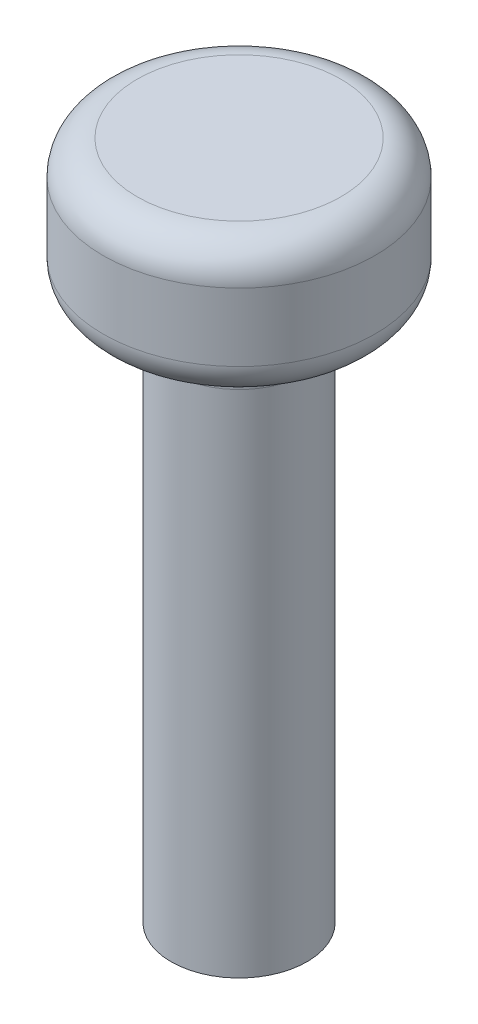
SolidWorks part; units mm, degrees
material "AISI 1020 Steel, Cold Rolled"
ref_plane "Front Plane" through (0, 0, 0) normal (0, 0, 1) x (1, 0, 0)
ref_plane "Top Plane" through (0, 0, 0) normal (0, 1, 0) x (1, 0, 0)
ref_plane "Right Plane" through (0, 0, 0) normal (1, 0, 0) x (0, 0, -1)
sketch "Sketch1" plane through (0, 0, 0) normal (0, 1, 0) x (1, 0, 0)
  circle A0 centre (0, 0) radius 1
  dimension "D1" = 2
extrude "Boss-Extrude1" add sketch "Sketch1" along normal blind 8
sketch "Sketch2" plane through (0, 8, 0) normal (0, 1, 0) x (1, 0, 0)
  circle A0 centre (0, 0) radius 2
  dimension "D1" = 4
extrude "Boss-Extrude2" add sketch "Sketch2" along normal blind 2
fillet "Fillet1" radius 0.5 1 edges at (0, 8, 1)
fillet "Fillet2" radius 0.5 2 edges at (0, 10, 2) (0, 8, 2)
